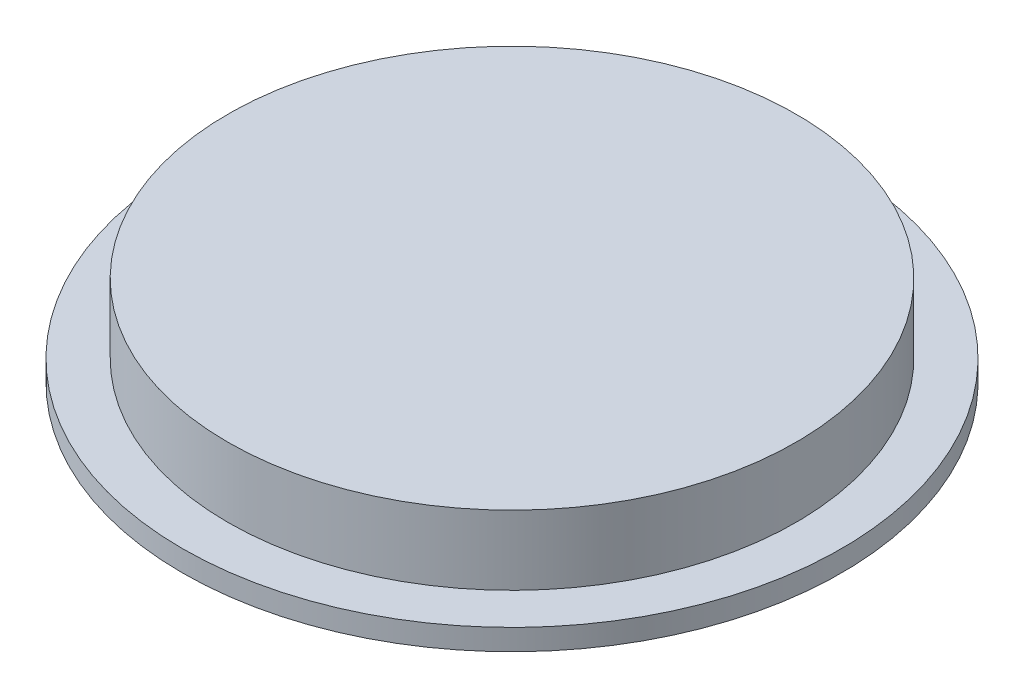
SolidWorks part; units mm, degrees
other "Camera1"
ref_plane "Front Plane" through (0, 0, 0) normal (0, 0, 1) x (1, 0, 0)
ref_plane "Top Plane" through (0, 0, 0) normal (0, 1, 0) x (1, 0, 0)
ref_plane "Right Plane" through (0, 0, 0) normal (1, 0, 0) x (0, 0, -1)
sketch "Sketch1" plane through (0, 0, 0) normal (0, 0, 1) x (1, 0, 0)
  line L0 (0, 45.2932) -> (0, -50.5102) construction
  line L1 (0, 13.5169) -> (51.9716, 13.5169)
  line L4 (60.279, -3.0367) -> (60.279, 0.8169)
  line L5 (60.279, 0.8169) -> (51.9716, 0.8169)
  line L6 (51.9716, 0.8169) -> (51.9716, 13.5169)
  line L7 (60.279, -3.0367) -> (47.1598, -3.0367)
  line L8 (47.1598, -3.0367) -> (38.1, 1.6707)
  line L9 (38.1, 1.6707) -> (0, 1.6707)
  line L10 (0, 13.5169) -> (0, 1.6707)
  dimension "D1" = 38.1
  dimension "D2" = 12.7
revolve "Revolve1" add sketch "Sketch1" angle 360 about L0
ref_plane "mate to root" through (0, 0.8169, 0) normal (0, 1, 0) x (1, 0, 0)
ref_plane "inside of roof " through (0, 13.5169, 0) normal (0, 1, 0) x (1, 0, 0)
